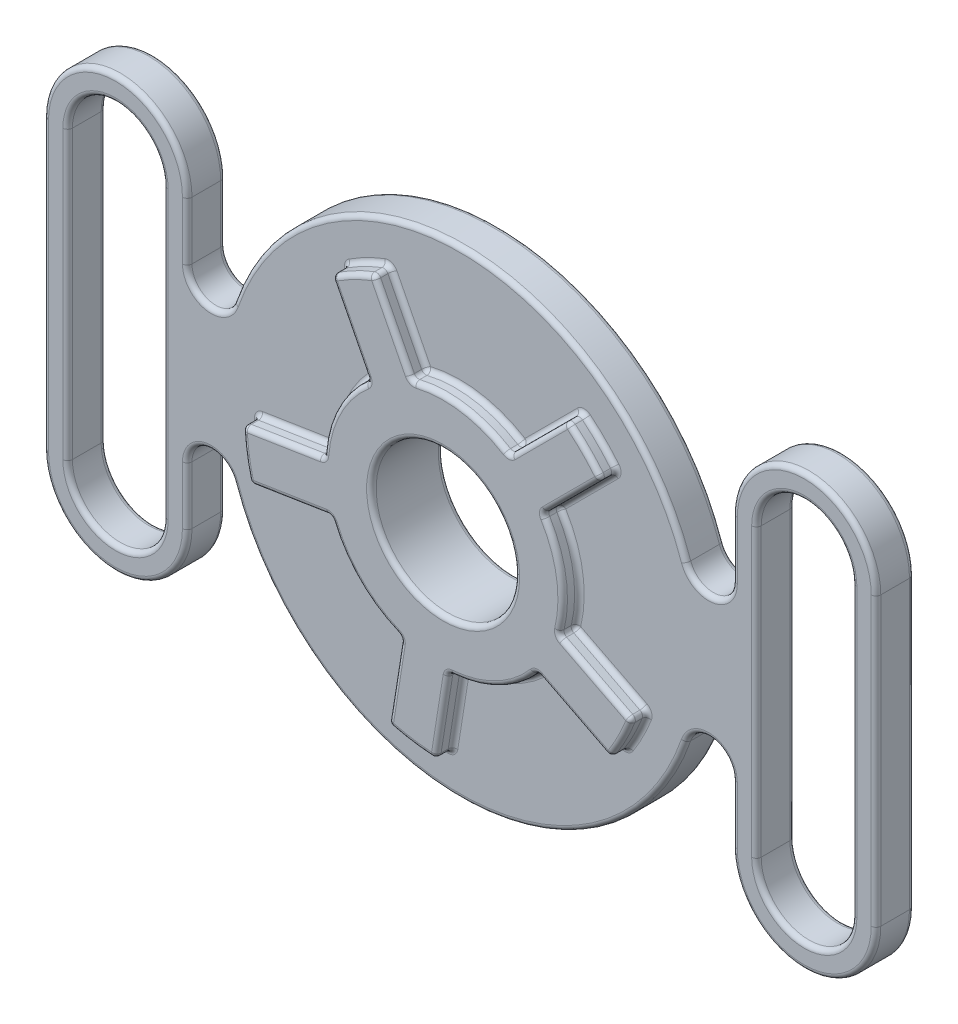
SolidWorks part; units mm, degrees
ref_plane "Front Plane" through (0, 0, 0) normal (0, 0, 1) x (1, 0, 0)
ref_plane "Top Plane" through (0, 0, 0) normal (0, 1, 0) x (1, 0, 0)
ref_plane "Right Plane" through (0, 0, 0) normal (1, 0, 0) x (0, 0, -1)
sketch "Sketch1" plane through (0, 0, 0) normal (0, 0, 1) x (1, 0, 0)
  line L0 (0, 0) -> (0, 37948.7671) construction
  line L1 (0, 0) -> (37948.7671, 0) construction
  line L2 (13.7643, 20.8697) -> (25.9325, 33.0379)
  line L3 (20.8697, 13.7643) -> (33.0379, 25.9325)
  line L4 (0, 0) -> (29.6985, 29.6985) construction
  line L5 (24.1017, -6.6416) -> (39.4345, -14.454)
  line L6 (19.5397, -15.5948) -> (34.8726, -23.4073)
  line L7 (1.1313, -24.9744) -> (-1.5607, -41.971)
  line L8 (-8.7935, -23.4025) -> (-11.4855, -40.3991)
  line L9 (-23.4025, -8.7935) -> (-40.3991, -11.4855)
  line L10 (-24.9744, 1.1313) -> (-41.971, -1.5607)
  line L11 (-15.5948, 19.5397) -> (-23.4073, 34.8726)
  line L12 (-6.6416, 24.1017) -> (-14.454, 39.4345)
  line L13 (-72, 30) -> (-72, -30) construction
  line L14 (-62, 30) -> (-62, -30)
  line L15 (-82, 30) -> (-82, -30)
  line L16 (-57, 30) -> (-57, 17.9165)
  line L17 (-87, 30) -> (-87, -30)
  line L18 (72, 30) -> (72, -30) construction
  line L19 (62, 30) -> (62, -30)
  line L20 (82, 30) -> (82, -30)
  line L21 (87, 30) -> (87, -30)
  line L22 (57, 30) -> (57, 17.9165)
  line L23 (-57, -17.9165) -> (-57, -30)
  line L24 (57, -17.9165) -> (57, -30)
  line L25 (-57, 30) -> (-57, -30) construction
  circle A0 centre (0, 0) radius 15
  arc A1 (13.7643, 20.8697) -> (-6.6416, 24.1017) centre (0, 0) ccw
  arc A2 (-41.971, -1.5607) -> (-40.3991, -11.4855) centre (0, 0) ccw
  arc A3 (-47.2727, -16.2877) -> (47.2727, -16.2877) centre (0, 0) ccw
  arc A4 (-15.5948, 19.5397) -> (-24.9744, 1.1313) centre (0, 0) ccw
  arc A5 (-23.4025, -8.7935) -> (-8.7935, -23.4025) centre (0, 0) ccw
  arc A6 (1.1313, -24.9744) -> (19.5397, -15.5948) centre (0, 0) ccw
  arc A7 (24.1017, -6.6416) -> (20.8697, 13.7643) centre (0, 0) ccw
  arc A8 (-11.4855, -40.3991) -> (-1.5607, -41.971) centre (0, 0) ccw
  arc A9 (-14.454, 39.4345) -> (-23.4073, 34.8726) centre (0, 0) ccw
  arc A10 (33.0379, 25.9325) -> (25.9325, 33.0379) centre (0, 0) ccw
  arc A11 (34.8726, -23.4073) -> (39.4345, -14.454) centre (0, 0) ccw
  arc A12 (-62, 30) -> (-82, 30) centre (-72, 30) ccw
  arc A13 (-82, -30) -> (-62, -30) centre (-72, -30) ccw
  arc A14 (-87, -30) -> (-57, -30) centre (-72, -30) ccw
  arc A15 (-57, 30) -> (-87, 30) centre (-72, 30) ccw
  arc A16 (-57, 17.9165) -> (-47.2727, 16.2877) centre (-52, 17.9165) ccw
  arc A17 (-57, -17.9165) -> (-47.2727, -16.2877) centre (-52, -17.9165) cw
  arc A18 (62, 30) -> (82, 30) centre (72, 30) cw
  arc A19 (82, -30) -> (62, -30) centre (72, -30) cw
  arc A20 (57, -17.9165) -> (47.2727, -16.2877) centre (52, -17.9165) ccw
  arc A21 (57, 17.9165) -> (47.2727, 16.2877) centre (52, 17.9165) cw
  arc A22 (57, 30) -> (87, 30) centre (72, 30) cw
  arc A23 (87, -30) -> (57, -30) centre (72, -30) cw
  arc A24 (47.2727, 16.2877) -> (-47.2727, 16.2877) centre (0, 0) ccw
  point P15 (-72, 0)
  point P34 (0, 0)
  point P52 (72, 0)
  dimension "D1" = 30
  dimension "D2" = 50
  dimension "D3" = 84
  dimension "D4" = 100
  dimension "D8" = 10
  dimension "D11" = 5
  dimension "D5" = 10.0485
  dimension "D6" = 45
  dimension "D7" = 60
  dimension "D9" = 72
  dimension "D10" = 5
extrude "Boss-Extrude1" add sketch "Sketch1" along normal mid plane 15 contours L6 A11 L5 A7 L3 A10 L2 A1 L12 A9 L11 A4 L10 A2 L9 A5 L8 A8 L7 A6 A0 region at (20.6625, 26.1397, 0)
extrude "Boss-Extrude2" add sketch "Sketch1<3>" along normal mid plane 8 contours A21 A24 A16 L16 A15 L17 A14 L23 A17 A3 A20 L24 A23 L21 A22 L22 L20 A19 L19 A18 A11 L6 A6 L7 A8 L8 A5 L9 A2 L10 A4 L11 A9 L12 A1 L2 A10 L3 A7 L5 A13 L15 A12 L14 region at (-59.0069, 23.9582, 0)
sketch "Sketch1<3>" plane through (0, 0, 0) normal (0, 0, 1) x (1, 0, 0) same geometry as "Sketch1"
fillet "Fillet2" radius 1 170 edges at (34.8726, -23.4073, 5.75) (34.8726, -23.4073, -5.75) (39.4345, -14.454, 5.75) (39.4345, -14.454, -5.75) (24.1017, -6.6416, 5.75) (24.1017, -6.6416, -5.75) (20.8697, 13.7643, 5.75) (20.8697, 13.7643, -5.75) (33.0379, 25.9325, 5.75) (33.0379, 25.9325, -5.75) (25.9325, 33.0379, 5.75) (25.9325, 33.0379, -5.75) (13.7643, 20.8697, 5.75) (13.7643, 20.8697, -5.75) (-6.6416, 24.1017, 5.75) (-6.6416, 24.1017, -5.75) (-14.454, 39.4345, 5.75) (-14.454, 39.4345, -5.75) (-23.4073, 34.8726, 5.75) (-23.4073, 34.8726, -5.75) (-15.5948, 19.5397, 5.75) (-15.5948, 19.5397, -5.75) (-24.9744, 1.1313, 5.75) (-24.9744, 1.1313, -5.75) (-41.971, -1.5607, 5.75) (-41.971, -1.5607, -5.75) (-40.3991, -11.4855, 5.75) (-40.3991, -11.4855, -5.75) (-23.4025, -8.7935, 5.75) (-23.4025, -8.7935, -5.75) (-8.7935, -23.4025, 5.75) (-8.7935, -23.4025, -5.75) (-11.4855, -40.3991, 5.75) (-11.4855, -40.3991, -5.75) (-1.5607, -41.971, 5.75) (-1.5607, -41.971, -5.75) (1.1313, -24.9744, 5.75) (1.1313, -24.9744, -5.75) (19.5397, -15.5948, 5.75) (19.5397, -15.5948, -5.75) (11.3498, -22.2752, 7.5) (-0.2147, -33.4727, 7.5) (-6.5702, -41.4829, 7.5) (-10.1395, -31.9008, 7.5) (-17.6777, -17.6777, 7.5) (-31.9008, -10.1395, 7.5) (-41.4829, -6.5702, 7.5) (-33.4727, -0.2147, 7.5) (-22.2752, 11.3498, 7.5) (-19.5011, 27.2062, 7.5) (-19.0676, 37.4223, 7.5) (-10.5478, 31.7681, 7.5) (3.9109, 24.6922, 7.5) (19.8484, 26.9538, 7.5) (29.6985, 29.6985, 7.5) (26.9538, 19.8484, 7.5) (24.6922, 3.9109, 7.5) (31.7681, -10.5478, 7.5) (37.4223, -19.0676, 7.5) (27.2062, -19.5011, 7.5) (15, 0, 7.5) (11.3498, -22.2752, -7.5) (-0.2147, -33.4727, -7.5) (-6.5702, -41.4829, -7.5) (-10.1395, -31.9008, -7.5) (-17.6777, -17.6777, -7.5) (-31.9008, -10.1395, -7.5) (-41.4829, -6.5702, -7.5) (-33.4727, -0.2147, -7.5) (-22.2752, 11.3498, -7.5) (-19.5011, 27.2062, -7.5) (-19.0676, 37.4223, -7.5) (-10.5478, 31.7681, -7.5) (3.9109, 24.6922, -7.5) (19.8484, 26.9538, -7.5) (29.6985, 29.6985, -7.5) (26.9538, 19.8484, -7.5) (24.6922, 3.9109, -7.5) (31.7681, -10.5478, -7.5) (37.4223, -19.0676, -7.5) (27.2062, -19.5011, -7.5) (15, 0, -7.5) (57, 23.9582, 4) (72, 45, 4) (87, 0, 4) (72, -45, 4) (57, -23.9582, 4) (52.8257, -12.9851, 4) (0, -50, 4) (-52.8257, -12.9851, 4) (-57, -23.9582, 4) (-72, -45, 4) (-87, 0, 4) (-72, 45, 4) (-57, 23.9582, 4) (-52.8257, 12.9851, 4) (0, 50, 4) (52.8257, 12.9851, 4) (-62, 0, 4) (-72, 40, 4) (-82, 0, 4) (-72, -40, 4) (31.7681, -10.5478, 4) (24.6922, 3.9109, 4) (26.9538, 19.8484, 4) (29.6985, 29.6985, 4) (19.8484, 26.9538, 4) (3.9109, 24.6922, 4) (-10.5478, 31.7681, 4) (-19.0676, 37.4223, 4) (-19.5011, 27.2062, 4) (-22.2752, 11.3498, 4) (-33.4727, -0.2147, 4) (-41.4829, -6.5702, 4) (-31.9008, -10.1395, 4) (-17.6777, -17.6777, 4) (-10.1395, -31.9008, 4) (-6.5702, -41.4829, 4) (-0.2147, -33.4727, 4) (11.3498, -22.2752, 4) (27.2062, -19.5011, 4) (37.4223, -19.0676, 4) (72, 40, 4) (62, 0, 4) (72, -40, 4) (82, 0, 4) (57, 23.9582, -4) (72, 45, -4) (87, 0, -4) (72, -45, -4) (57, -23.9582, -4) (52.8257, -12.9851, -4) (0, -50, -4) (-52.8257, -12.9851, -4) (-57, -23.9582, -4) (-72, -45, -4) (-87, 0, -4) (-72, 45, -4) (-57, 23.9582, -4) (-52.8257, 12.9851, -4) (0, 50, -4) (52.8257, 12.9851, -4) (-62, 0, -4) (-72, 40, -4) (-82, 0, -4) (-72, -40, -4) (31.7681, -10.5478, -4) (24.6922, 3.9109, -4) (26.9538, 19.8484, -4) (29.6985, 29.6985, -4) (19.8484, 26.9538, -4) (3.9109, 24.6922, -4) (-10.5478, 31.7681, -4) (-19.0676, 37.4223, -4) (-19.5011, 27.2062, -4) (-22.2752, 11.3498, -4) (-33.4727, -0.2147, -4) (-41.4829, -6.5702, -4) (-31.9008, -10.1395, -4) (-17.6777, -17.6777, -4) (-10.1395, -31.9008, -4) (-6.5702, -41.4829, -4) (-0.2147, -33.4727, -4) (11.3498, -22.2752, -4) (27.2062, -19.5011, -4) (37.4223, -19.0676, -4) (72, 40, -4) (62, 0, -4) (72, -40, -4) (82, 0, -4)
